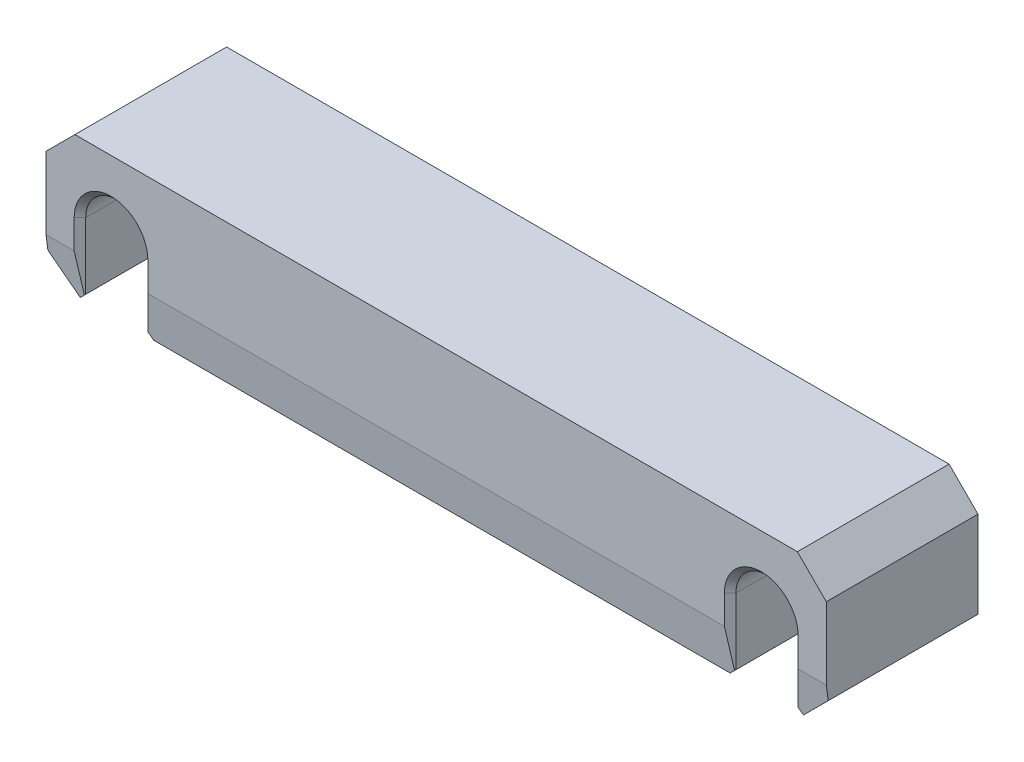
SolidWorks part; units mm, degrees
ref_plane "Front" through (0, 0, 0) normal (0, 0, 1) x (1, 0, 0)
ref_plane "Top" through (0, 0, 0) normal (0, 1, 0) x (1, 0, 0)
ref_plane "Right" through (0, 0, 0) normal (1, 0, 0) x (0, 0, -1)
sketch "Sketch1" plane through (0, 0, 0) normal (0, 0, 1) x (1, 0, 0)
  line L1 (0, 0) -> (54, 0)
  line L2 (0, 0) -> (0, 10)
  line L3 (0, 10) -> (54, 10)
  line L4 (54, 0) -> (54, 10)
  dimension "D1" = 54
  dimension "D2" = 10
extrude "Boss-Extrude1" add sketch "Sketch1" along normal blind 10.5
sketch "Sketch2" plane through (0, 0, 10.5) normal (0, 0, 1) x (1, 0, 0)
  line L0 (0, 0) -> (54, 0) construction
  line L1 (0, 10) -> (0, 0) construction
  circle A0 centre (4.5, 5) radius 2.15
  circle A1 centre (49.5, 5) radius 2.15
  dimension "D1" = 4.3
  dimension "D2" = 5
  dimension "D3" = 45
  dimension "D4" = 4.5
extrude "Cut-Extrude1" cut sketch "Sketch2" against normal blind 10.5
sketch "Sketch3" plane through (0, 0, 10.5) normal (0, 0, 1) x (1, 0, 0)
  line L0 (0, 0) -> (54, 0) construction
  line L1 (2.35, 5) -> (6.65, 5)
  line L2 (2.35, 5) -> (2.35, 0)
  line L3 (2.35, 0) -> (6.65, 0)
  line L4 (6.65, 5) -> (6.65, 0)
  line L6 (47.35, 5) -> (51.65, 5)
  line L7 (47.35, 5) -> (47.35, 0)
  line L8 (47.35, 0) -> (51.65, 0)
  line L9 (51.65, 5) -> (51.65, 0)
  circle A0 centre (4.5, 5) radius 2.15 construction
  circle A1 centre (49.5, 5) radius 2.15 construction
  dimension "D1" = 4.3
  dimension "D2" = 4.3
  dimension "D3" = 5
  dimension "D4" = 5
extrude "Cut-Extrude2" cut sketch "Sketch3" against normal blind 10.5
chamfer "Chamfer3" distance 0.4 distance2 3 3 edges at (1.175, 0, 10.5) (52.825, 0, 10.5) (27, 0, 10.5) first distance on face at (1.175, 0, 5.25) first distance on face at (52.825, 0, 5.25) first distance on face at (27, 0, 5.25)
chamfer "Chamfer1" distance 2 angle 45 4 edges at (54, 0, 5.05) (54, 10, 5.25) (0, 0, 5.05) (0, 10, 5.25)
chamfer "Chamfer2" distance 0.4 angle 45 12 edges at (49.5, 7.15, 10.5) (49.5, 7.15, 0) (4.5, 7.15, 10.5) (4.5, 7.15, 0) (51.65, 2.5, 0) (47.35, 2.5, 0) (51.65, 4, 10.5) (47.35, 4, 10.5) (6.65, 2.5, 0) (2.35, 2.5, 0) (6.65, 4, 10.5) (2.35, 4, 10.5)
chamfer "Chamfer4" distance 0.4 angle 45 4 edges at (47.35, 0, 5.25) (6.65, 0, 5.25) (51.65, 0, 5.25) (2.35, 0, 5.25)
